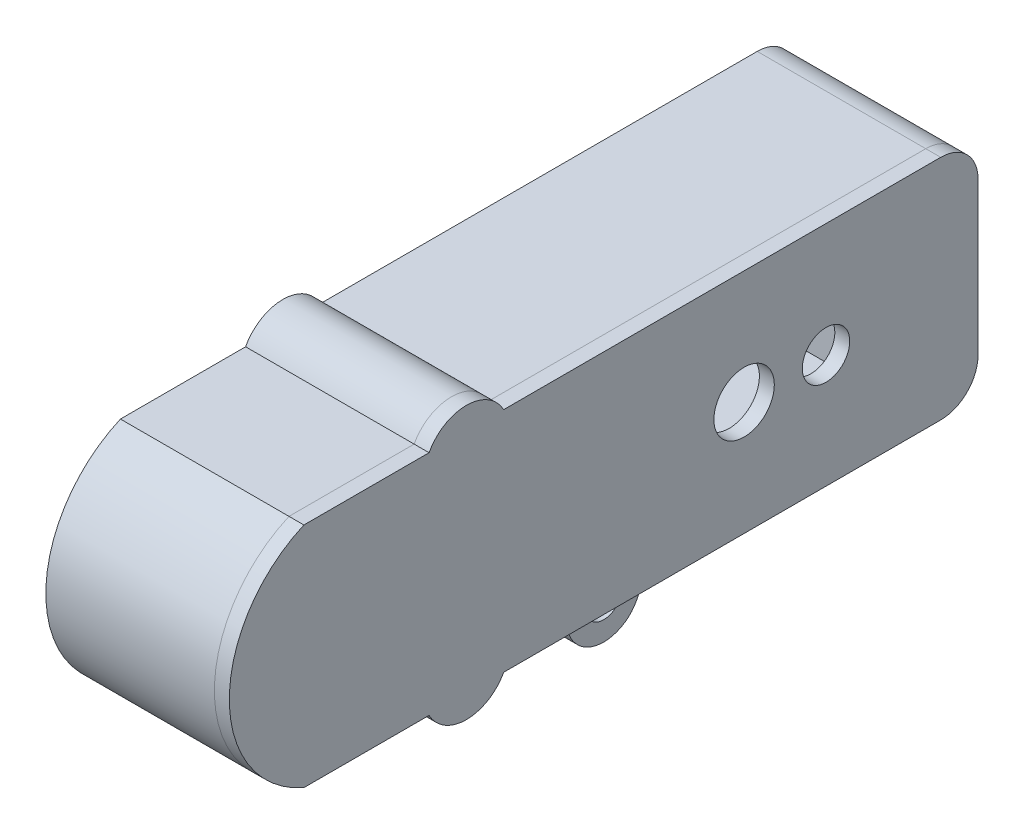
SolidWorks part; units mm, degrees
ref_plane "Front Plane" through (0, 0, 0) normal (0, 0, 1) x (1, 0, 0)
ref_plane "Top Plane" through (0, 0, 0) normal (0, 1, 0) x (1, 0, 0)
ref_plane "Right Plane" through (0, 0, 0) normal (1, 0, 0) x (0, 0, -1)
sketch "Sketch1" plane through (0, 0, 0) normal (1, 0, 0) x (0, 0, -1)
  line L0 (-25.32, -11.25) -> (8.38, -11.25) construction
  line L1 (20.38, -15.25) -> (-70, -15.25)
  line L2 (20.38, -15.25) -> (20.38, 15.25)
  line L3 (20.38, 15.25) -> (-70, 15.25)
  line L4 (-70, -15.25) -> (-70, 15.25) construction
  line L5 (11.38, -8.25) -> (11.38, 8.25) construction
  line L6 (-25.32, -11.25) -> (8.38, -11.25) construction
  line L7 (11.38, -8.25) -> (11.38, 8.25) construction
  line L8 (8.38, 11.25) -> (-25.32, 11.25) construction
  line L9 (8.38, 11.25) -> (-25.32, 11.25) construction
  line L10 (8.38, 15.25) -> (8.38, 11.25) construction
  line L11 (20.38, 8.25) -> (11.38, 8.25) construction
  line L12 (8.38, -11.25) -> (8.38, -15.25) construction
  line L13 (16.38, 2) -> (16.38, -2) construction
  line L14 (16.38, 2) -> (16.38, -2) construction
  line L15 (16.38, 2) -> (20.38, 2) construction
  line L17 (-70, 0) -> (-80, 0) construction
  arc A0 (-70, 15.25) -> (-70, -15.25) centre (-63.3719, 0) ccw
  dimension "D2" = 10
  dimension "D1" = 4
extrude "Boss-Extrude1" add sketch "Sketch1" against normal blind 3
fillet "Fillet1" radius 5 2 edges at (-1.5, -15.25, -20.38) (-1.5, 15.25, -20.38)
sketch "Sketch2" plane through (0, 0, 0) normal (1, 0, 0) x (0, 0, -1)
  line L0 (-69.3438, -12.25) -> (15.38, -12.25)
  line L1 (17.38, -10.25) -> (17.38, 10.25)
  line L2 (15.38, 12.25) -> (-69.3438, 12.25)
  line L3 (-70, -15.25) -> (15.38, -15.25)
  line L4 (20.38, -10.25) -> (20.38, 10.25)
  line L5 (15.38, 15.25) -> (-70, 15.25)
  line L6 (-70, -15.25) -> (15.38, -15.25)
  line L7 (20.38, -10.25) -> (20.38, 10.25)
  line L8 (15.38, 15.25) -> (-70, 15.25)
  arc A0 (15.38, -12.25) -> (17.38, -10.25) centre (15.38, -10.25) ccw
  arc A1 (17.38, 10.25) -> (15.38, 12.25) centre (15.38, 10.25) ccw
  arc A2 (-69.3438, 12.25) -> (-69.3438, -12.25) centre (-63.3719, 0) ccw
  arc A3 (15.38, -15.25) -> (20.38, -10.25) centre (15.38, -10.25) ccw
  arc A4 (20.38, 10.25) -> (15.38, 15.25) centre (15.38, 10.25) ccw
  arc A5 (-70, 15.25) -> (-70, -15.25) centre (-63.3719, 0) ccw
  arc A8 (-70, 15.25) -> (-70, -15.25) centre (-63.3719, 0) ccw
  arc A9 (15.38, -15.25) -> (20.38, -10.25) centre (15.38, -10.25) ccw
  arc A10 (15.38, 15.25) -> (20.38, 10.25) centre (15.38, 10.25) cw
  arc A12 (15.38, -15.25) -> (20.38, -10.25) centre (15.38, -10.25) ccw construction
  arc A13 (20.38, 10.25) -> (15.38, 15.25) centre (15.38, 10.25) ccw construction
  dimension "D1" = 0
  dimension "D2" = 3
extrude "Boss-Extrude2" add sketch "Sketch2" along normal offset from surface (19.6 mm away) 1 offset beyond the face yes
sketch "Sketch3" plane through (0, 0, 0) normal (1, 0, 0) x (0, 0, -1)
  line L0 (-34.62, 12.25) -> (-34.62, 11.25)
  line L1 (-69.3438, 12.25) -> (15.38, 12.25) construction
  line L2 (-34.62, 11.25) -> (10.38, 11.25)
  line L3 (11.38, 10.25) -> (11.38, -12.25)
  line L4 (15.38, -12.25) -> (-69.3438, -12.25) construction
  line L5 (11.38, -12.25) -> (15.38, -12.25)
  line L6 (11.38, 8.25) -> (11.38, -8.25) construction
  line L7 (-25.32, 11.25) -> (8.38, 11.25) construction
  line L8 (15.38, 12.25) -> (-69.3438, 12.25) construction
  line L9 (17.38, -10.25) -> (17.38, 10.25) construction
  line L10 (15.38, 12.25) -> (-34.62, 12.25)
  line L11 (17.38, -10.25) -> (17.38, 10.25)
  arc A0 (10.38, 11.25) -> (11.38, 10.25) centre (10.38, 10.25) cw
  arc A1 (17.38, 10.25) -> (15.38, 12.25) centre (15.38, 10.25) ccw construction
  arc A2 (15.38, -12.25) -> (17.38, -10.25) centre (15.38, -10.25) ccw construction
  arc A3 (17.38, 10.25) -> (15.38, 12.25) centre (15.38, 10.25) ccw
  arc A4 (15.38, -12.25) -> (17.38, -10.25) centre (15.38, -10.25) ccw
  dimension "D1" = 1
  dimension "D2" = 45
extrude "Boss-Extrude5" add sketch "Sketch3" along normal up to surface (18.6 mm away)
sketch "Sketch5" plane through (18.6, 0, 0) normal (1, 0, 0) x (0, 0, -1)
  line L4 (17.38, 10.25) -> (17.38, -10.25) construction
  line L5 (10.38, -3.5) -> (17.38, -3.5)
  line L6 (10.38, -3.5) -> (10.38, 3.5)
  line L7 (10.38, 3.5) -> (17.38, 3.5)
  line L12 (17.38, -3.5) -> (17.38, 3.5)
  line L13 (10.38, -3.5) -> (17.38, 3.5) construction
  line L14 (10.38, 3.5) -> (17.38, -3.5) construction
  arc A2 (15.18, 0) -> (12.58, 0) centre (13.88, 0) ccw construction
  arc A3 (15.18, 0) -> (12.58, 0) centre (13.88, 0) ccw construction
extrude "Cut-Extrude1" cut sketch "Sketch5" against normal offset from surface (11.8 mm away) 1 offset beyond the face yes
sketch "Sketch6" plane through (0, 0, 0) normal (1, 0, 0) x (0, 0, -1)
  line L0 (-49.019, 14.805) -> (-47.419, 14.805) construction
  line L1 (-49.019, 14.805) -> (-47.419, 14.805) construction
  line L2 (-49.019, -15.055) -> (-47.419, -15.055) construction
  line L3 (-49.019, -15.055) -> (-47.419, -15.055) construction
  line L4 (-49.019, 14.805) -> (-49.019, -15.055) construction
  line L5 (-47.419, -15.055) -> (-47.419, 14.805) construction
  line L6 (-50.019, 15.805) -> (-46.419, 15.805)
  line L7 (-46.419, -16.055) -> (-46.419, 15.805)
  line L8 (-50.019, -16.055) -> (-46.419, -16.055)
  line L9 (-50.019, 15.805) -> (-50.019, -16.055)
  dimension "D1" = 1
extrude "Cut-Extrude2" cut sketch "Sketch6" along normal through all
sketch "Sketch7" plane through (-3, 0, 0) normal (-1, 0, 0) x (0, 0, 1)
  line L0 (70, 15.25) -> (50.019, 15.25) construction
  line L1 (46.419, 15.25) -> (-15.38, 15.25) construction
  line L6 (48.219, 15.25) -> (48.219, 18.25) construction
  line L7 (50.019, 15.25) -> (46.419, 15.25) construction
  line L8 (53.219, 15.25) -> (43.219, 15.25)
  line L9 (0, 0) -> (12.8243, 0) construction
  line L10 (48.219, -15.25) -> (48.219, -18.25) construction
  line L11 (53.219, -15.25) -> (43.219, -15.25)
  arc A0 (53.219, 15.25) -> (43.219, 15.25) centre (48.219, 12.5833) ccw
  arc A1 (53.219, -15.25) -> (43.219, -15.25) centre (48.219, -12.5833) cw
  dimension "D1" = 10
  dimension "D2" = 3
extrude "Boss-Extrude6" add sketch "Sketch7" against normal up to surface (22.6 mm away) up to face at (19.6, 0, 62.0525)
sketch "Sketch8" plane through (19.6, 0, 0) normal (1, 0, 0) x (0, 0, -1)
  line L5 (-70, -15.25) -> (-53.219, -15.25)
  line L6 (-43.219, -15.25) -> (15.38, -15.25)
  line L7 (20.38, -10.25) -> (20.38, 10.25)
  line L8 (15.38, 15.25) -> (-43.219, 15.25)
  line L9 (-53.219, 15.25) -> (-70, 15.25)
  line L10 (-70, -15.25) -> (-53.219, -15.25)
  line L11 (-43.219, -15.25) -> (15.38, -15.25)
  line L12 (20.38, -10.25) -> (20.38, 10.25)
  line L13 (15.38, 15.25) -> (-43.219, 15.25)
  line L14 (-53.219, 15.25) -> (-70, 15.25)
  arc A5 (-53.219, -15.25) -> (-43.219, -15.25) centre (-48.219, -12.5833) ccw
  arc A6 (15.38, -15.25) -> (20.38, -10.25) centre (15.38, -10.25) ccw
  arc A7 (15.38, -15.25) -> (20.38, -10.25) centre (15.38, -10.25) ccw
  arc A8 (-43.219, 15.25) -> (-53.219, 15.25) centre (-48.219, 12.5833) ccw
  arc A9 (-70, 15.25) -> (-70, -15.25) centre (-63.3719, 0) ccw
  arc A13 (-43.219, 15.25) -> (-53.219, 15.25) centre (-48.219, 12.5833) ccw
  arc A14 (-70, 15.25) -> (-70, -15.25) centre (-63.3719, 0) ccw
  arc A15 (-53.219, -15.25) -> (-43.219, -15.25) centre (-48.219, -12.5833) ccw
  arc A16 (20.38, 10.25) -> (15.38, 15.25) centre (15.38, 10.25) ccw
  arc A18 (20.38, 10.25) -> (15.38, 15.25) centre (15.38, 10.25) ccw
  dimension "D1" = 0
extrude "Boss-Extrude7" add sketch "Sketch8" along normal blind 2 separate body
ref_plane "Plane2" through (9.3, 0, 0) normal (1, 0, 0) x (0, 0, -1)
sketch "Sketch9" plane through (9.3, 0, 0) normal (1, 0, 0) x (0, 0, -1)
  line L0 (-27.5, -15.25) -> (-27.5, -20.75)
  line L1 (-43.219, -15.25) -> (15.38, -15.25) construction
  line L2 (-17.5, -20.75) -> (-17.5, -15.25)
  line L3 (-17.5, -15.25) -> (-27.5, -15.25)
  line L4 (-22.5, -25.75) -> (-22.5, -15.25) construction
  line L5 (-22.5, -20.75) -> (-72.5, -20.75) construction
  line L6 (-72.5, -20.75) -> (-72.5, -23) construction
  arc A0 (-27.5, -20.75) -> (-17.5, -20.75) centre (-22.5, -20.75) ccw
  dimension "D1" = 10
  dimension "D2" = 5.5
  dimension "D3" = 50
extrude "Boss-Extrude8" add sketch "Sketch9" along normal mid plane 10
sketch "Sketch10" [suppressed] plane through (-3, 0, 0) normal (-1, 0, 0) x (0, 0, 1)
  line L0 (72.2754, -39.9249) -> (69.4884, -40.8677)
  line L1 (-6.0881, -39.9249) -> (70, -39.9249) construction
  line L2 (72.2754, -39.9249) -> (70, -39.9249)
  line L3 (0, 0) -> (15.2828, 0) construction
  line L4 (72.2754, 39.9249) -> (69.4884, 40.8677)
  line L5 (72.2754, 39.9249) -> (70, 39.9249)
  line L6 (-4.7, 0) -> (70, -39.9249) construction
  arc A0 (70, 39.9249) -> (70, -39.9249) centre (-4.7, 0) ccw construction
  arc A1 (69.4884, -40.8677) -> (70, -39.9249) centre (-4.7, 0) ccw
  arc A2 (69.4884, 40.8677) -> (70, 39.9249) centre (-4.7, 0) cw
  point P12 (70.8819, -40.3963)
  dimension "D1" = 1
extrude "Cut-Extrude3" [suppressed] cut sketch "Sketch10" against normal through all
sketch "Sketch11" plane through (-3, 0, 0) normal (-1, 0, 0) x (0, 0, 1)
  line L0 (55.019, -4.125) -> (53.0647, -4.125) construction
  line L1 (55.019, 3.875) -> (55.019, -4.125) construction
  line L2 (55.019, 3.875) -> (53.0647, 3.875) construction
  line L3 (47.419, 9.875) -> (49.019, 9.875) construction
  line L4 (49.019, -10.125) -> (47.419, -10.125) construction
  line L5 (41.419, -6.125) -> (44.2041, -6.125) construction
  line L6 (41.419, -6.125) -> (41.419, 5.875) construction
  line L7 (41.419, 5.875) -> (44.2041, 5.875) construction
  line L8 (55.019, -4.125) -> (53.0647, -4.125) construction
  line L9 (55.019, 3.875) -> (55.019, -4.125) construction
  line L10 (55.019, 3.875) -> (53.0647, 3.875) construction
  line L11 (47.419, 9.875) -> (49.019, 9.875) construction
  line L12 (49.019, -10.125) -> (47.419, -10.125) construction
  line L13 (41.419, -6.125) -> (44.2041, -6.125) construction
  line L14 (41.419, -6.125) -> (41.419, 5.875) construction
  line L15 (41.419, 5.875) -> (44.2041, 5.875) construction
  line L16 (47.419, 9.875) -> (47.419, 5.875) construction
  line L17 (47.419, 5.875) -> (44.2041, 5.875) construction
  line L18 (53.0647, 3.875) -> (49.019, 3.875) construction
  line L19 (49.019, 3.875) -> (49.019, 9.875) construction
  line L20 (44.2041, -6.125) -> (47.419, -6.125) construction
  line L21 (47.419, -6.125) -> (47.419, -10.125) construction
  line L22 (49.019, -10.125) -> (49.019, -4.125) construction
  line L23 (49.019, -4.125) -> (53.0647, -4.125) construction
  line L24 (56.019, -5.125) -> (53.0647, -5.125)
  line L25 (50.019, -5.125) -> (53.0647, -5.125)
  line L26 (50.019, -11.125) -> (50.019, -5.125)
  line L27 (50.019, -11.125) -> (46.419, -11.125)
  line L28 (46.419, -7.125) -> (46.419, -11.125)
  line L29 (44.2041, -7.125) -> (46.419, -7.125)
  line L30 (40.419, -7.125) -> (44.2041, -7.125)
  line L31 (40.419, -7.125) -> (40.419, 6.875)
  line L32 (40.419, 6.875) -> (44.2041, 6.875)
  line L33 (46.419, 6.875) -> (44.2041, 6.875)
  line L34 (46.419, 10.875) -> (46.419, 6.875)
  line L35 (46.419, 10.875) -> (50.019, 10.875)
  line L36 (50.019, 4.875) -> (50.019, 10.875)
  line L37 (53.0647, 4.875) -> (50.019, 4.875)
  line L38 (56.019, 4.875) -> (53.0647, 4.875)
  line L39 (56.019, 4.875) -> (56.019, -5.125)
  dimension "D1" = 1
extrude "Cut-Extrude4" cut sketch "Sketch11" against normal up to next (3 mm away)
sketch "Sketch12" plane through (0, 0, 0) normal (1, 0, 0) x (0, 0, -1)
  line L1 (-58.97, 8.5) -> (-58.97, -8.5) construction
  line L2 (-25.62, 12.25) -> (-58.97, 12.25)
  line L3 (-25.62, 12.25) -> (-25.62, -12.25)
  line L4 (-25.62, -12.25) -> (-58.97, -12.25)
  line L5 (-58.97, 12.25) -> (-58.97, -12.25)
  line L9 (-69.3438, -12.25) -> (-50.019, -12.25) construction
  line L10 (-50.019, 12.25) -> (-69.3438, 12.25) construction
  line L11 (-25.62, -10.95) -> (-25.62, 10.95) construction
extrude "Cut-Extrude5" cut sketch "Sketch12" along normal through all and the other way blind 2
sketch "Sketch13" plane through (19.6, 0, 0) normal (-1, 0, 0) x (0, 0, 1)
  line L0 (34.62, 4.575) -> (28.12, 4.575)
  line L1 (28.12, 4.575) -> (28.12, -4.575)
  line L2 (28.12, -4.575) -> (34.62, -4.575)
  line L3 (34.62, -4.575) -> (34.62, 4.575)
  line L4 (32.62, 2.575) -> (30.12, 2.575)
  line L5 (32.62, -2.575) -> (32.62, 2.575)
  line L6 (30.12, -2.575) -> (32.62, -2.575)
  line L7 (30.12, 2.575) -> (30.12, -2.575)
  line L8 (32.62, 2.575) -> (30.12, 2.575) construction
  line L9 (32.62, -2.575) -> (32.62, 2.575) construction
  line L10 (30.12, -2.575) -> (32.62, -2.575) construction
  line L11 (30.12, 2.575) -> (30.12, -2.575) construction
  circle A0 centre (0, 0) radius 2.68 construction
  circle A1 centre (0, 0) radius 2.68 construction
  arc A2 (13.0296, 0) -> (8.9296, 0) centre (10.9796, 0) ccw construction
  arc A3 (13.0296, 0) -> (8.9296, 0) centre (10.9796, 0) ccw construction
  circle A4 centre (0, 0) radius 3.18
  circle A5 centre (10.9796, 0) radius 4.05
  dimension "D3" = 2
  dimension "D1" = 0
  dimension "D2" = 0.5
  dimension "D4" = 2
extrude "Cut-Extrude6" cut sketch "Sketch13" against normal up to next (2 mm away)
sketch "Sketch14" plane through (21.6, 0, 0) normal (1, 0, 0) x (0, 0, -1)
  line L0 (-28.12, 4.575) -> (-28.12, -4.575) construction
  line L1 (-34.62, 4.575) -> (-28.12, 4.575) construction
  line L2 (-34.62, -4.575) -> (-34.62, 4.575) construction
  line L3 (-28.12, 4.575) -> (-28.12, -4.575)
  line L4 (-34.62, 4.575) -> (-28.12, 4.575)
  line L5 (-34.62, -4.575) -> (-34.62, 4.575)
  line L6 (-28.12, -4.575) -> (-34.62, -4.575) construction
  line L7 (-28.12, -4.575) -> (-34.62, -4.575)
extrude "Boss-Extrude9" add sketch "Sketch14" against normal offset from surface (1.17 mm away) 0.5
sketch "Sketch15" plane through (0, 0, 0) normal (1, 0, 0) x (0, 0, -1)
  line L0 (-58.97, 12.25) -> (-69.3438, 12.25) construction
  line L1 (-69.3438, -12.25) -> (-58.97, -12.25) construction
  line L2 (-69.3438, 12.25) -> (-69.3438, -12.25) construction
  line L3 (-58.97, -12.25) -> (-58.97, 12.25)
  line L6 (-61.97, -12.25) -> (-61.97, 12.25)
  line L7 (-61.97, 12.25) -> (-69.3438, 12.25)
  line L8 (-69.3438, -12.25) -> (-61.97, -12.25)
  line L9 (-66.1688, 0) -> (-58.97, 0) construction
  line L10 (-58.97, 12.25) -> (-58.97, -12.25) construction
  line L16 (-58.97, 12.25) -> (-69.3438, 12.25)
  line L17 (-69.3438, -12.25) -> (-58.97, -12.25)
  arc A1 (-69.3438, 12.25) -> (-69.3438, -12.25) centre (-63.3719, 0) ccw
  circle A3 centre (-69.3438, 0) radius 3.175 construction
  arc A9 (-69.3438, 12.25) -> (-69.3438, -12.25) centre (-63.3719, 0) ccw
  point P3 (-69.3438, 12.0065)
  point P4 (-69.6246, 12.1091)
  point P17 (-61.97, 0)
  dimension "D2" = 6.35
  dimension "D3" = 3
  dimension "D1" = 0
extrude "Boss-Extrude10" add sketch "Sketch15" along normal up to surface (18.6 mm away) up to face at (18.6, 9.3902, -4.0827)
sketch "Sketch16" [suppressed] plane through (21.6, 0, 0) normal (1, 0, 0) x (0, 0, -1)
  line L0 (-66.0069, 15.25) -> (-66.0069, -15.25) construction
  line L1 (-63.3399, 2.1489) -> (-63.3399, -2.1489)
  line L2 (-63.3399, 0) -> (-62.5819, 0) construction
  line L3 (-63.3399, 0) -> (-69.4319, 0) construction
  line L4 (-69.1819, 0) -> (-69.1819, -0.549) construction
  line L5 (-69.1819, -0.549) -> (-63.3399, -0.549) construction
  circle A0 centre (-66.0069, 0) radius 3.175 construction
  arc A1 (-63.3399, 2.1489) -> (-63.3399, -2.1489) centre (-66.0069, 0) ccw
  circle A2 centre (-66.0069, 0) radius 3.425 construction
  dimension "D1" = 6.35
  dimension "D3" = 5.842
  dimension "D2" = 0.25
extrude "Cut-Extrude7" [suppressed] cut sketch "Sketch16" against normal through all
sketch "Sketch17" [suppressed] plane through (21.6, 0, 0) normal (1, 0, 0) x (0, 0, -1)
  circle A0 centre (-66.0069, 0) radius 3.425
  arc A1 (-63.3399, 2.1489) -> (-63.3399, -2.1489) centre (-66.0069, 0) ccw construction
extrude "Cut-Extrude8" [suppressed] cut sketch "Sketch17" against normal up to surface (2 mm away) up to face at (21.6, 0, -3.18)
hole_wizard "M4 Clearance Hole1" positions "Sketch18" profile "Sketch19" hole size "M4" standard "ANSI Metric" end condition through all
sketch "Sketch18" plane through (14.3, 0, 0) normal (1, 0, 0) x (0, 0, -1)
  arc A0 (-27.5, -20.75) -> (-17.5, -20.75) centre (-22.5, -20.75) ccw construction
  point P0 (-22.5, -20.75)
sketch "Sketch19" plane through (14.3, -20.75, 22.5) normal (0, 1, 0) x (0, 0, -1)
  line L0 (0, 0) -> (0, 17.3)
  line L1 (0, 17.3) -> (2.4, 17.3)
  line L2 (2.4, 17.3) -> (2.4, 0)
  line L5 (2.4, 0) -> (0, 0)
  line L11 (0, -6.35) -> (0, 107.95) construction
  dimension "Thru Hole Dia." = 4.8
  dimension "Thru Hole Depth" = 17.3
sketch "Sketch20" plane through (9.3, 0, 0) normal (1, 0, 0) x (0, 0, -1)
  line L3 (-27.5, -15.25) -> (-27.5, -20.75)
  line L4 (-17.5, -20.75) -> (-17.5, -15.25)
  line L5 (-17.5, -15.25) -> (-27.5, -15.25)
  line L6 (-27.5, -15.25) -> (-27.5, -20.75)
  line L7 (-17.5, -20.75) -> (-17.5, -15.25)
  line L8 (-17.5, -15.25) -> (-27.5, -15.25)
  arc A1 (-27.5, -20.75) -> (-17.5, -20.75) centre (-22.5, -20.75) ccw
  arc A2 (-27.5, -20.75) -> (-17.5, -20.75) centre (-22.5, -20.75) ccw
  dimension "D1" = 0
extrude "Cut-Extrude9" cut sketch "Sketch20" against normal mid plane 0.762
